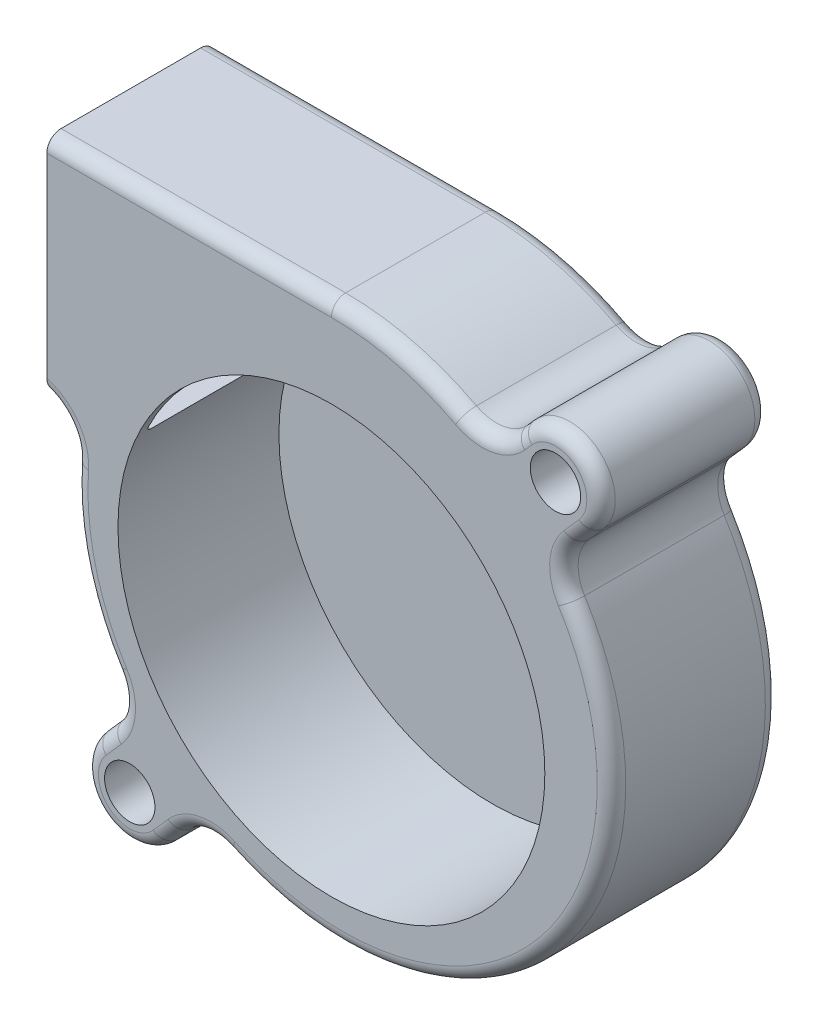
SolidWorks part; units mm, degrees
ref_plane "Front Plane" through (0, 0, 0) normal (0, 0, 1) x (1, 0, 0)
ref_plane "Top Plane" through (0, 0, 0) normal (0, 1, 0) x (1, 0, 0)
ref_plane "Right Plane" through (0, 0, 0) normal (1, 0, 0) x (0, 0, -1)
sketch "Sketch1" plane through (0, 0, 0) normal (0, 0, 1) x (1, 0, 0)
  line L0 (-18, -20) -> (20, 23) construction
  line L1 (-25.4, 7) -> (-25.4, 27)
  line L2 (-25.4, 27) -> (0, 27)
  line L3 (0, 0) -> (0, 27) construction
  line L4 (-25.4, 7) -> (-22.3613, 7)
  line L5 (20, 23) -> (16.9547, 25.6912) construction
  line L6 (-18, -20) -> (-21.0453, -17.3088) construction
  line L7 (20, 23) -> (23.0453, 20.3088) construction
  line L8 (-18, -20) -> (-14.9547, -22.6912) construction
  line L9 (16.9547, 25.6912) -> (14.2108, 22.5862)
  line L10 (23.0453, 20.3088) -> (19.7085, 16.533)
  line L11 (-11.618, -18.9154) -> (-14.9547, -22.6912)
  line L12 (-17.7085, -13.533) -> (-21.0453, -17.3088)
  circle A0 centre (0, 0) radius 19.05
  circle A1 centre (-18, -20) radius 2.2479
  circle A2 centre (20, 23) radius 2.2479
  circle A3 centre (1, 1.5) radius 24 construction
  arc A4 (16.9547, 25.6912) -> (23.0453, 20.3088) centre (20, 23) cw
  arc A5 (-21.0453, -17.3088) -> (-14.9547, -22.6912) centre (-18, -20) ccw
  arc A6 (19.7085, 16.533) -> (-11.618, -18.9154) centre (1, 1.5) cw
  arc A7 (-17.7085, -13.533) -> (-22.3613, 7) centre (1, 1.5) cw
  arc A8 (0, 27) -> (14.2108, 22.5862) centre (0, 1.9167) cw
  dimension "D1" = 38.1
  dimension "D2" = 4.4958
  dimension "D7" = 48
  dimension "D11" = 4.064
  dimension "D3" = 18
  dimension "D4" = 20
  dimension "D5" = 20
  dimension "D6" = 23
  dimension "D8" = 25.4
  dimension "D9" = 20
  dimension "D10" = 27
extrude "Boss-Extrude2" add sketch "Sketch1" along normal blind 15
fillet "Fillet1" radius 3.81 5 edges at (14.2108, 22.5862, 7.5) (19.7085, 16.533, 7.5) (-11.618, -18.9154, 7.5) (-17.7085, -13.533, 7.5) (-22.3613, 7, 7.5)
fillet "Fillet2" radius 1.27 30 edges at (-12.7, 27, 0) (6.0164, 26.2678, 0) (14.1429, 23.7379, 0) (16.6328, 25.3268, 0) (22.6912, 26.0453, 0) (22.3763, 19.5519, 0) (20.7651, 16.5836, 0) (18.9839, -14.3927, 0) (-11.5382, -19.9702, 0) (-14.2858, -21.9342, 0) (-20.6912, -23.0453, 0) (-20.3763, -16.5519, 0) (-18.7651, -13.5836, 0) (-22.2822, -4.3257, 0) (-23.5361, 5.4921, 15) (-22.2822, -4.3257, 15) (-18.7651, -13.5836, 15) (-20.3763, -16.5519, 15) (-20.6912, -23.0453, 15) (-14.2858, -21.9342, 15) (-11.5382, -19.9702, 15) (18.9839, -14.3927, 15) (20.7651, 16.5836, 15) (22.3763, 19.5519, 15) (22.6912, 26.0453, 15) (16.6328, 25.3268, 15) (14.1429, 23.7379, 15) (6.0164, 26.2678, 15) (-23.5361, 5.4921, 0) (-12.7, 27, 15)
sketch "Sketch2" plane through (0, 0, 0) normal (0, 0, -1) x (-1, 0, 0)
  circle A0 centre (0, 0) radius 19.05
  circle A1 centre (0, 0) radius 19.05 construction
extrude "Boss-Extrude3" add sketch "Sketch2" against normal blind 0.635
sketch "Sketch4" plane through (-25.4, 0, 0) normal (-1, 0, 0) x (0, 0, 1)
  line L8 (1.27, 7.8128) -> (13.73, 7.8128)
  line L9 (13.73, 26.1872) -> (1.27, 26.1872)
  line L10 (14.1872, 8.3338) -> (14.1872, 25.73)
  line L11 (0.8128, 25.73) -> (0.8128, 8.3338)
  line L12 (1.27, 7.8128) -> (13.73, 7.8128)
  line L13 (13.73, 26.1872) -> (1.27, 26.1872)
  line L14 (14.1872, 8.3338) -> (14.1872, 25.73)
  line L15 (0.8128, 25.73) -> (0.8128, 8.3338)
  arc A4 (14.1872, 25.73) -> (13.73, 26.1872) centre (13.73, 25.73) ccw
  arc A5 (1.27, 26.1872) -> (0.8128, 25.73) centre (1.27, 25.73) ccw
  arc A6 (14.1872, 25.73) -> (13.73, 26.1872) centre (13.73, 25.73) ccw
  arc A7 (1.27, 26.1872) -> (0.8128, 25.73) centre (1.27, 25.73) ccw
  spline S4 degree 3 poles (1414.7596, -3730.5927) (110.4104, 101.0464) (-3.6441, 13.5329) (0.9797, 7.9308) (1.0284, 7.8897) (6.0516, 5.2387) (57.961, 102.9733) (-2917.397, 2740.4225) knots -27.476964 -27.476964 -27.476964 -27.476964 0.5 0.5 0.75 0.75 22.561281 22.561281 22.561281 22.561281 only from (0.8128, 8.3338) to (1.27, 7.8128)
  spline S5 degree 3 poles (2299.9339, 3288.4244) (-66.7076, 55.1369) (10.5556, 3.7233) (18.4128, 13.2647) (-81.3949, 98.1474) (-1619.2357, -3640.5027) knots -21.084026 -21.084026 -21.084026 -21.084026 0.5 0.5 27.294882 27.294882 27.294882 27.294882 only from (13.73, 7.8128) to (14.1872, 8.3338)
  spline S6 degree 3 poles (0.8128, 8.3338) (0.8128, 8.205) (0.8568, 8.0796) (0.9797, 7.9308) (1.0284, 7.8897) (1.1423, 7.8297) (1.2054, 7.8128) (1.27, 7.8128) knots 0 0 0 0 0.5 0.5 0.75 0.75 1 1 1 1
  spline S7 degree 3 poles (13.73, 7.8128) (13.8591, 7.8128) (13.9799, 7.8815) (14.1423, 8.0788) (14.1872, 8.2051) (14.1872, 8.3338) knots 0 0 0 0 0.5 0.5 1 1 1 1
  dimension "D1" = 0.8128
extrude "Cut-Extrude1" cut sketch "Sketch4" against normal blind 26.035
ref_plane "Plane1" through (0, 17, 0) normal (0, 1, 0) x (-1, 0, 0)
